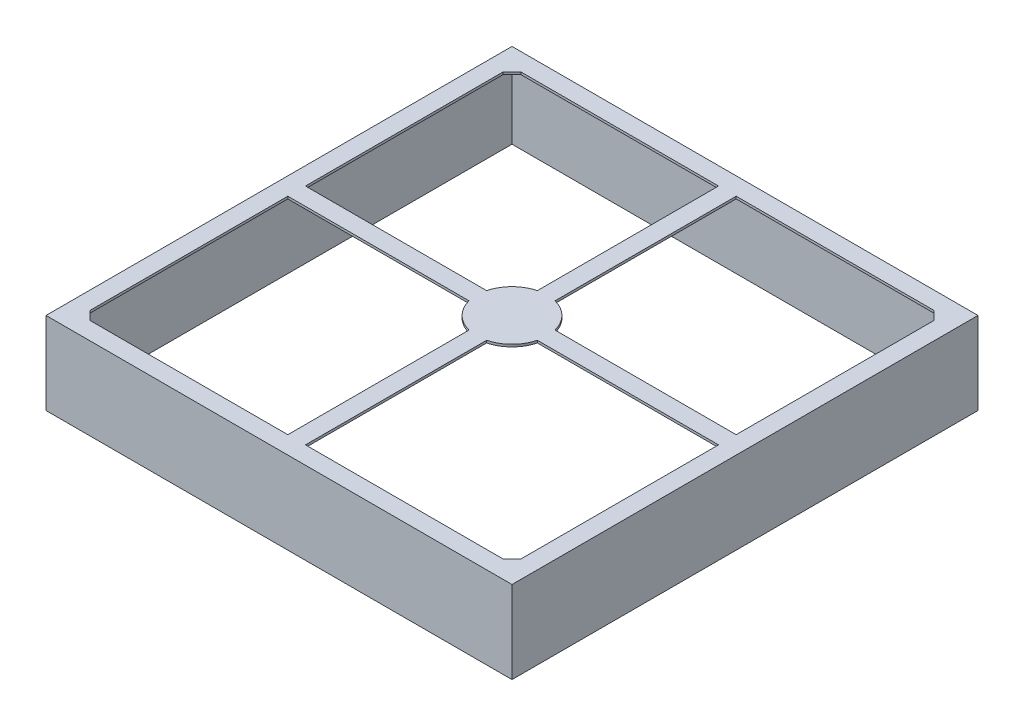
SolidWorks part; units mm, degrees
material "Magnesium Alloy"
ref_plane "Front Plane" through (0, 0, 0) normal (0, 0, 1) x (1, 0, 0)
ref_plane "Top Plane" through (0, 0, 0) normal (0, 1, 0) x (1, 0, 0)
ref_plane "Right Plane" through (0, 0, 0) normal (1, 0, 0) x (0, 0, -1)
sketch "Sketch1" plane through (0, 0, 0) normal (0, 1, 0) x (1, 0, 0)
  line L1 (-19.8, -19.8) -> (19.8, -19.8)
  line L2 (-19.8, -19.8) -> (-19.8, 19.8)
  line L3 (-19.8, 19.8) -> (19.8, 19.8)
  line L4 (19.8, -19.8) -> (19.8, 19.8)
  line L5 (-19.8, -19.8) -> (19.8, 19.8) construction
  line L6 (-19.8, 19.8) -> (19.8, -19.8) construction
  point P0 (0, 0)
  dimension "D1" = 39.6
extrude "Boss-Extrude1" add sketch "Sketch1" along normal blind 7
shell "Shell2" thickness 0.2 removed face at (0, 0, 0)
sketch "Sketch2" plane through (0, 0, 0) normal (0, 1, 0) x (1, 0, 0)
  line L0 (19.8, 19.8) -> (-19.8, 19.8) construction
  line L1 (17.55, -18.3) -> (0.75, -18.3)
  line L2 (18.3, -17.55) -> (18.3, -0.75)
  line L3 (17.55, 18.3) -> (0.75, 18.3)
  line L4 (-18.3, -17.55) -> (-18.3, -0.75)
  line L5 (18.3, -18.3) -> (-18.3, 18.3) construction
  line L6 (18.3, 18.3) -> (-18.3, -18.3) construction
  line L7 (0, 19.8) -> (0, -18.3) construction
  line L8 (19.8, 0) -> (-19.8, 0) construction
  line L9 (-0.75, 18.3) -> (-0.75, 2.9047)
  line L10 (18.3, 0.75) -> (2.9047, 0.75)
  line L11 (0.75, 18.3) -> (0.75, 2.9047)
  line L12 (18.3, -0.75) -> (2.9047, -0.75)
  line L13 (-2.9047, -0.75) -> (-18.3, -0.75)
  line L14 (18.3, -0.75) -> (-18.3, -0.75) construction
  line L15 (-2.9047, 0.75) -> (-18.3, 0.75)
  line L16 (18.3, 0.75) -> (-18.3, 0.75) construction
  line L17 (-0.75, -2.9047) -> (-0.75, -18.3)
  line L18 (-0.75, 18.3) -> (-0.75, -18.3) construction
  line L19 (0.75, -2.9047) -> (0.75, -18.3)
  line L20 (0.75, 18.3) -> (0.75, -18.3) construction
  line L21 (-18.3, 0.75) -> (-18.3, 17.55)
  line L22 (-0.75, -18.3) -> (-17.55, -18.3)
  line L23 (18.3, 0.75) -> (18.3, 17.55)
  line L24 (-0.75, 18.3) -> (-17.55, 18.3)
  line L25 (-19.8, 19.8) -> (-19.8, -19.8) construction
  line L26 (18.3, 0) -> (-18.3, 0) construction
  line L27 (-17.55, 18.3) -> (-18.3, 17.55)
  line L28 (18.3, 17.55) -> (17.55, 18.3)
  line L29 (19.8, -19.8) -> (19.8, 19.8) construction
  line L30 (0, 18.3) -> (0, -18.3) construction
  line L31 (17.55, -18.3) -> (18.3, -17.55)
  line L32 (-17.55, -18.3) -> (-18.3, -17.55)
  arc A0 (-2.9047, -0.75) -> (-0.75, -2.9047) centre (0, 0) ccw
  arc A1 (0.75, -2.9047) -> (2.9047, -0.75) centre (0, 0) ccw
  arc A2 (2.9047, 0.75) -> (0.75, 2.9047) centre (0, 0) ccw
  arc A3 (-0.75, 2.9047) -> (-2.9047, 0.75) centre (0, 0) ccw
  point P0 (0, 0)
  dimension "D2" = 6
  dimension "D1" = 1.5
  dimension "D5" = 1.5
  dimension "D3" = 0.75
  dimension "D4" = 0.75
extrude "Cut-Extrude1" cut sketch "Sketch2" along normal through all
